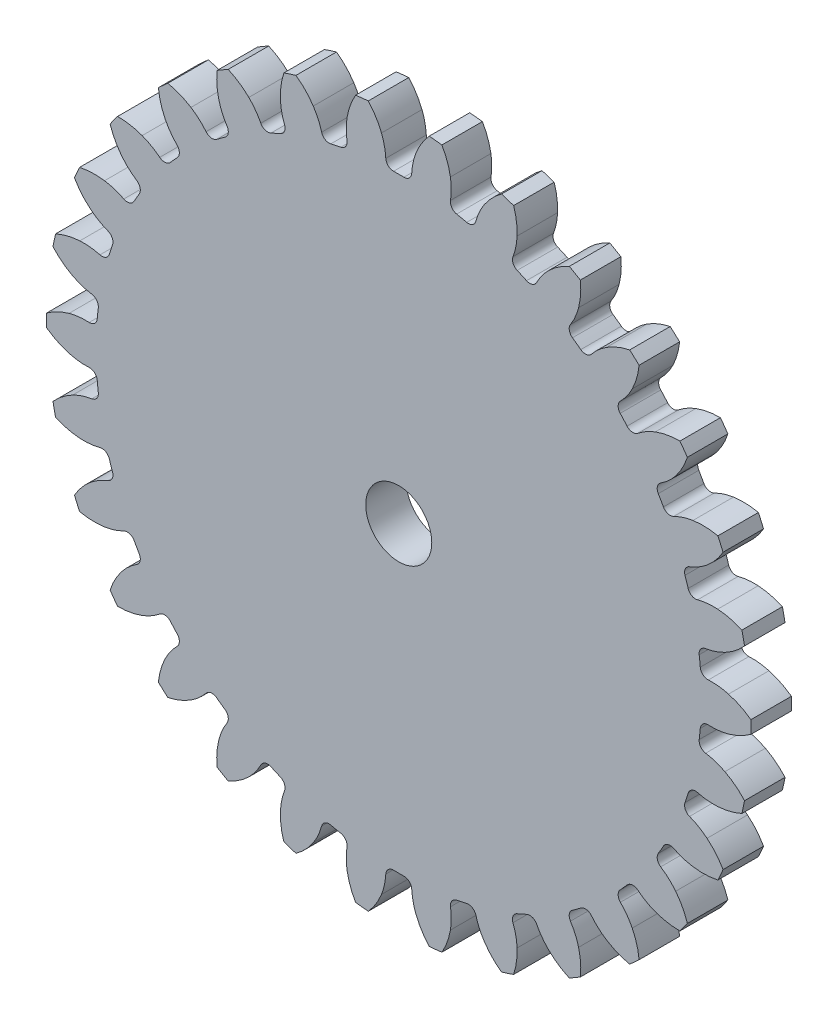
SolidWorks part; units mm, degrees
ref_plane "Front Plane" through (0, 0, 0) normal (0, 0, 1) x (1, 0, 0)
ref_plane "Top Plane" through (0, 0, 0) normal (0, 1, 0) x (1, 0, 0)
ref_plane "Right Plane" through (0, 0, 0) normal (1, 0, 0) x (0, 0, -1)
sketch "Sketch1" plane through (0, 0, 0) normal (0, 0, 1) x (1, 0, 0)
  line L0 (0, 0) -> (47.625, 0) construction
  line L1 (47.625, 0) -> (50.8, 0) construction
  circle A0 centre (0, 0) radius 50.8
  circle A1 centre (0, 0) radius 47.625 construction
  dimension "D2" = 95.25
  dimension "D1" = 3.175
extrude "GEAR_BASE" add sketch "Sketch1" along normal mid plane 5.842
sketch "Sketch2" plane through (0, 0, 2.921) normal (0, 0, 1) x (1, 0, 0)
  line L0 (0, 0) -> (43.6562, 0) construction
  line L1 (43.6562, 0) -> (47.625, 0) construction
  line L2 (0, 0) -> (-50.8, 0) construction
  line L3 (0, 0) -> (-47.5597, -2.494) construction
  line L4 (-47.5597, -2.494) -> (-48.4854, 15.1594) construction
  line L5 (0, 0) -> (-49.6899, -10.5619) construction
  line L6 (-47.5597, -2.494) -> (-43.5589, -2.9143) construction
  line L7 (-47.0389, -7.4487) -> (-43.2129, -6.2057) construction
  line L8 (0, 0) -> (-47.0389, -7.4487) construction
  line L9 (-47.5597, -2.494) -> (-50.7917, -0.9177) construction
  line L10 (-47.0389, -7.4487) -> (-49.8726, -9.6625) construction
  line L11 (-47.0389, -7.4487) -> (-46.5204, -9.8882) construction
  line L12 (-47.0389, -7.4487) -> (-44.274, -24.9088) construction
  line L13 (-47.5597, -2.494) -> (-47.5597, 0) construction
  circle A0 centre (0, 0) radius 47.625 construction
  circle A1 centre (0, 0) radius 43.6562 construction
  circle A2 centre (0, 0) radius 50.8 construction
  arc A3 (-49.8726, -9.6625) -> (-50.7917, -0.9177) centre (0, 0) cw
  arc A4 (-43.4883, -3.8254) -> (-44.6549, -2.8132) centre (-44.5953, -3.9228) ccw
  arc A5 (-44.264, -6.5326) -> (-43.3334, -5.2999) centre (-44.4364, -5.4348) ccw
  arc A6 (-43.3334, -5.2999) -> (-43.4883, -3.8254) centre (0, 0) cw
  arc A7 (-49.8726, -9.6625) -> (-47.0389, -7.4487) centre (-42.4148, -16.2882) cw
  arc A8 (-50.7917, -0.9177) -> (-47.5597, -2.494) centre (-44.8744, 7.1137) ccw
  arc A9 (-47.0389, -7.4487) -> (-44.264, -6.5326) centre (-42.8676, -15.4226) cw
  arc A10 (-47.5597, -2.494) -> (-44.6549, -2.8132) centre (-45.1374, 6.173) ccw
  dimension "D1" = 95.25
  dimension "D11" = 1.1112
  dimension "D12" = 9.9758
  dimension "D2" = 3.9688
  dimension "D3" = 12
  dimension "D5" = 9
  dimension "D7" = 9
  dimension "D8" = 4.9821
  dimension "D9" = 20
  dimension "D10" = 20
  dimension "D6" = 2.494
  dimension "D4" = 2.494
extrude "GEAR_CUT" cut sketch "Sketch2" against normal through all
ref_axis "GEAR_AXIS" through (0, 0, -3.2131) along (0, 0, 1)
pattern_circular "GEAR_TEETH" count 30 over 360 about axis through (0, 0, -3.2131) along (0, 0, 1) of "GEAR_CUT"
sketch "Sketch3" plane through (0, 0, 2.921) normal (0, 0, 1) x (1, 0, 0)
  circle A0 centre (0, 0) radius 4.7625
  dimension "D1" = 9.525
extrude "BORE" cut sketch "Sketch3" against normal through all
equation "\"N_teeth\"= 30"
equation "\"pitch_diameter\"= \"N_teeth\" / \"Pitch\""
equation "\"Pitch\"= 8"
equation "\"addendum\"=1.000/\"Pitch\""
equation "\"face_width\"=0.23"
equation "\"deddendum\"=1.250/\"Pitch\""
equation "\"tooth_thickness\"=1.571/\"Pitch\""
equation "\"Pressure_Angle\"=20.000000"
equation "\"base_fillet\"=0.35/\"Pitch\""
equation "\"D1@Sketch1\"=\"addendum\""
equation "\"D2@Sketch1\"=\"pitch_diameter\""
equation "\"D1@GEAR_BASE\" = \"face_width\""
equation "\"D1@Sketch2\"= \"pitch_diameter\""
equation "\"D2@Sketch2\"=\"deddendum\""
equation "\"D4@Sketch2\"=\"tooth_thickness\"/2"
equation "\"D6@Sketch2\"=\"tooth_thickness\"/2"
equation "\"D9@Sketch2\"=\"Pressure_Angle\""
equation "\"D10@Sketch2\"=\"Pressure_Angle\""
equation "\"D11@Sketch2\"=\"base_fillet\""
equation "\"D12@Sketch2\"=2*\"tooth_thickness\""
equation "\"D3@Sketch2\" = 360 / \"N_teeth\""
equation "\"D1@GEAR_TEETH\" = \"N_teeth\""
